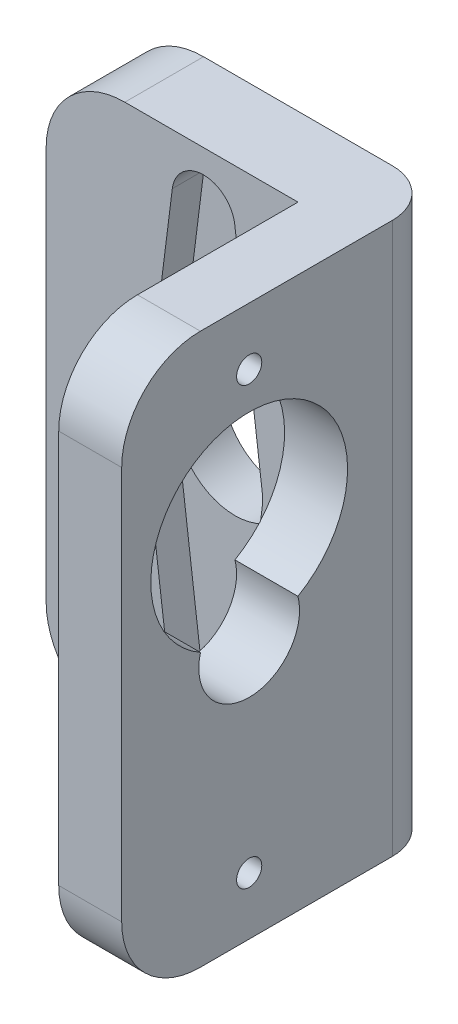
SolidWorks part; units mm, degrees
ref_plane "Front Plane" through (0, 0, 0) normal (0, 0, 1) x (1, 0, 0)
ref_plane "Top Plane" through (0, 0, 0) normal (0, 1, 0) x (1, 0, 0)
ref_plane "Right Plane" through (0, 0, 0) normal (1, 0, 0) x (0, 0, -1)
sketch "Sketch1" plane through (0, 0, 0) normal (0, 0, 1) x (1, 0, 0)
  line L0 (0, 0) -> (0, 14) construction
  line L1 (0, 0) -> (0, -14) construction
  line L2 (-3.7206, 0.4687) -> (-1.9843, 14.25) construction
  line L3 (10, -17.5) -> (-5, -17.5)
  line L4 (10, -17.5) -> (10, 17.5)
  line L5 (10, 17.5) -> (-5, 17.5)
  line L6 (-10, -12.5) -> (-10, 12.5)
  line L7 (10, -17.5) -> (-10, 17.5) construction
  line L8 (10, 17.5) -> (-10, -17.5) construction
  line L9 (-3.7206, -0.4687) -> (-1.9843, -14.25) construction
  line L10 (1.9843, -14.25) -> (3.7206, -0.4687) construction
  line L11 (1.9843, 14.25) -> (3.7206, 0.4687) construction
  arc A0 (-3.7206, 0.4687) -> (-3.7206, -0.4687) centre (0, 0) ccw construction
  arc A1 (1.9843, 14.25) -> (-1.9843, 14.25) centre (0, 14) ccw construction
  arc A2 (-1.9843, -14.25) -> (1.9843, -14.25) centre (0, -14) ccw construction
  arc A3 (-5, -17.5) -> (-10, -12.5) centre (-5, -12.5) cw
  arc A4 (-5, 17.5) -> (-10, 12.5) centre (-5, 12.5) ccw
  arc A5 (3.7206, -0.4687) -> (3.7206, 0.4687) centre (0, 0) ccw construction
  circle A6 centre (0, 0) radius 3.75
  dimension "D1" = 5
  dimension "D3" = 2
  dimension "D4" = 3.75
  dimension "D5" = 2
  dimension "D7" = 7.5
  dimension "D2" = 14
  dimension "D6" = 14
  dimension "D8" = 35
  dimension "D9" = 20
extrude "Boss-Extrude1" add sketch "Sketch1" against normal blind 5
sketch "Sketch3" plane through (0, 0, 0) normal (0, 0, 1) x (1, 0, 0)
  line L0 (0, 0) -> (-8.7328, 0) construction
  line L1 (0, 0) -> (0, 14) construction
  line L2 (0, 0) -> (6.3077, 0) construction
  line L3 (0, 0) -> (0, -14) construction
  line L4 (-1.9843, 14.25) -> (-3.7206, 0.4688)
  line L5 (-3.7206, -0.4688) -> (-1.9843, -14.25)
  line L6 (1.9843, 14.25) -> (3.7206, 0.4688)
  line L7 (1.9843, -14.25) -> (3.7206, -0.4687)
  arc A0 (1.9843, 14.25) -> (-1.9843, 14.25) centre (0, 14) ccw
  arc A1 (-1.9843, -14.25) -> (1.9843, -14.25) centre (0, -14) ccw
  arc A2 (-3.7206, 0.4688) -> (-3.7206, -0.4688) centre (0, 0) ccw
  arc A3 (3.7206, -0.4687) -> (3.7206, 0.4688) centre (0, 0) ccw
  dimension "D2" = 4
  dimension "D3" = 4
  dimension "D4" = 7.5
  dimension "D1" = 14
extrude "Cut-Extrude2" cut sketch "Sketch3" against normal blind 2
sketch "Sketch5" plane through (10, 0, 0) normal (1, 0, 0) x (0, 0, -1)
  line L0 (5, -17.5) -> (0, -17.5) construction
  line L1 (5, 17.5) -> (-10.2, 17.5)
  line L2 (5, 17.5) -> (5, -17.5)
  line L3 (5, -17.5) -> (-10.2, -17.5)
  line L4 (-15.2, 12.5) -> (-15.2, -12.5)
  line L5 (-7.1, 0) -> (-15.2, 0) construction
  line L6 (-7.1, 13.85) -> (-7.1, -13.85) construction
  line L7 (-13.2, -11.6) -> (-1, -11.6) construction
  line L8 (-13.2, -11.6) -> (-13.2, 11.6) construction
  line L9 (-13.2, 11.6) -> (-1, 11.6) construction
  line L10 (-1, -11.6) -> (-1, 11.6) construction
  line L11 (-13.2, -11.6) -> (-1, 11.6) construction
  line L12 (-13.2, 11.6) -> (-1, -11.6) construction
  line L13 (0, -17.5) -> (0, 17.5) construction
  circle A0 centre (-7.1, 13.85) radius 0.8
  circle A1 centre (-7.1, -13.85) radius 0.8
  arc A2 (-15.2, -12.5) -> (-10.2, -17.5) centre (-10.2, -12.5) ccw
  arc A3 (-15.2, 12.5) -> (-10.2, 17.5) centre (-10.2, 12.5) cw
  arc A4 (-4.0066, -0.1808) -> (-10.1934, -0.1808) centre (-7.1, 5.25) ccw
  arc A5 (-10.1934, -0.1808) -> (-4.0066, -0.1808) centre (-7.1, -1) ccw
  point P7 (-7.1, 0)
  point P16 (-7.1, 0)
  dimension "D4" = 1.6
  dimension "D6" = 5
  dimension "D1" = 12.2
  dimension "D2" = 23.2
  dimension "D3" = 2
  dimension "D5" = 27.7
  dimension "D7" = 1
extrude "Boss-Extrude2" add sketch "Sketch5" against normal blind 4
fillet "Fillet1" radius 3 1 edges at (10, 0, -5)
